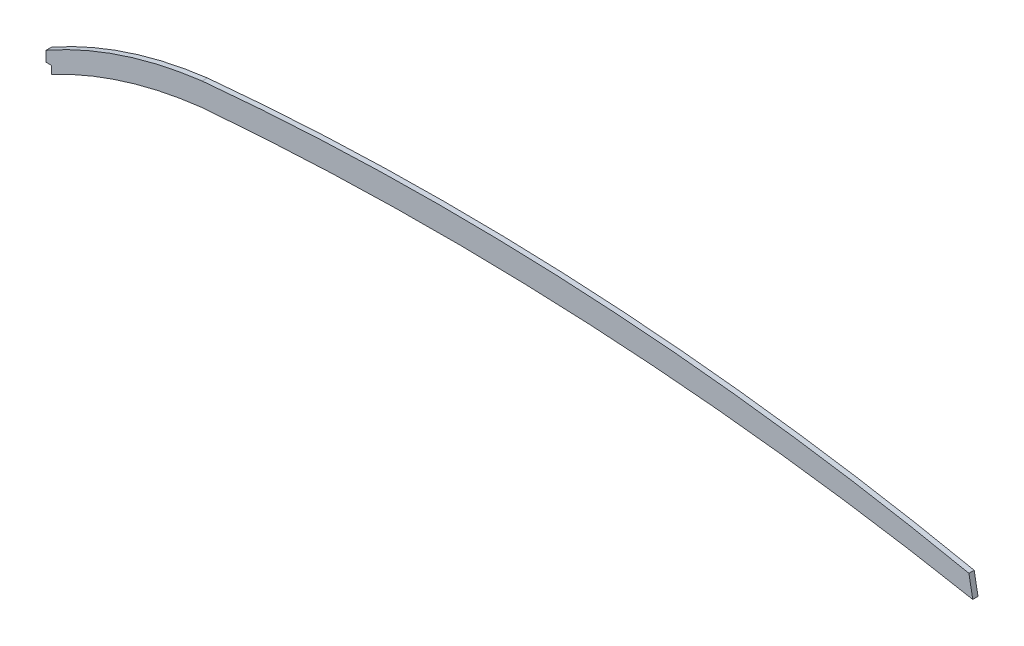
SolidWorks part; units mm, degrees
material "Balsa"
ref_plane "Front Plane" through (0, 0, 0) normal (0, 0, 1) x (1, 0, 0)
ref_plane "Top Plane" through (0, 0, 0) normal (0, 1, 0) x (1, 0, 0)
ref_plane "Right Plane" through (0, 0, 0) normal (1, 0, 0) x (0, 0, -1)
sketch "Sketch1" plane through (0, 0, 0) normal (0, 0, 1) x (1, 0, 0)
  line L2 (0, 0) -> (0, 169.3685) construction
  line L4 (93.98, 106.68) -> (556.5761, 106.68) construction
  line L9 (0, 106.68) -> (93.98, 106.68) construction
  line L14 (555.6382, 111.8229) -> (555.6382, 106.68) construction
  line L17 (555.6382, 111.8229) -> (557.917, 99.3265)
  line L19 (0, 106.68) -> (0, 93.98)
  line L20 (93.98, 137.668) -> (93.98, 123.7947) construction
  arc A6 (0, 106.68) -> (93.98, 137.668) centre (125.0054, -114.43) cw
  arc A8 (93.98, 137.668) -> (555.6382, 111.8229) centre (239.5165, -1398.7972) cw
  arc A9 (0, 93.98) -> (93.98, 123.7947) centre (122.3372, -128.6174) cw
  arc A25 (93.98, 123.7947) -> (557.917, 99.3265) centre (236.8486, -1577.8511) cw
  dimension "D4" = 254
  dimension "D2" = 93.98
  dimension "D8" = 1543.3426
  dimension "D9" = 100.334
  dimension "D3" = 30.988
  dimension "D12" = 254
  dimension "D14" = 1707.6328
  dimension "D1" = 106.68
  dimension "D5" = 462.5961
  dimension "D6" = 0.9378
  dimension "D7" = 5.1429
  dimension "D10" = 12.7025
  dimension "D11" = 12.7
  dimension "D13" = 13.8733
extrude "Boss-Extrude1" add sketch "Sketch1" along normal blind 3.175 contours A9 A25 L17 A8 A6 L19 region at (551.2665, 104.5698, 0)
sketch "Sketch2" plane through (0, 0, 3.175) normal (0, 0, 1) x (1, 0, 0)
  line L0 (0, 0) -> (0, 93.98) construction
  line L4 (0, 93.98) -> (3.3528, 93.98)
  line L5 (0, 93.98) -> (0, 100.457)
  line L6 (0, 100.457) -> (3.3528, 100.457)
  line L7 (3.3528, 93.98) -> (3.3528, 100.457)
  dimension "D1" = 93.98
  dimension "D2" = 6.477
  dimension "D3" = 3.3528
extrude "Cut-Extrude1" cut sketch "Sketch2" against normal through all
equation "\"slotwidth\"=0.167708"
